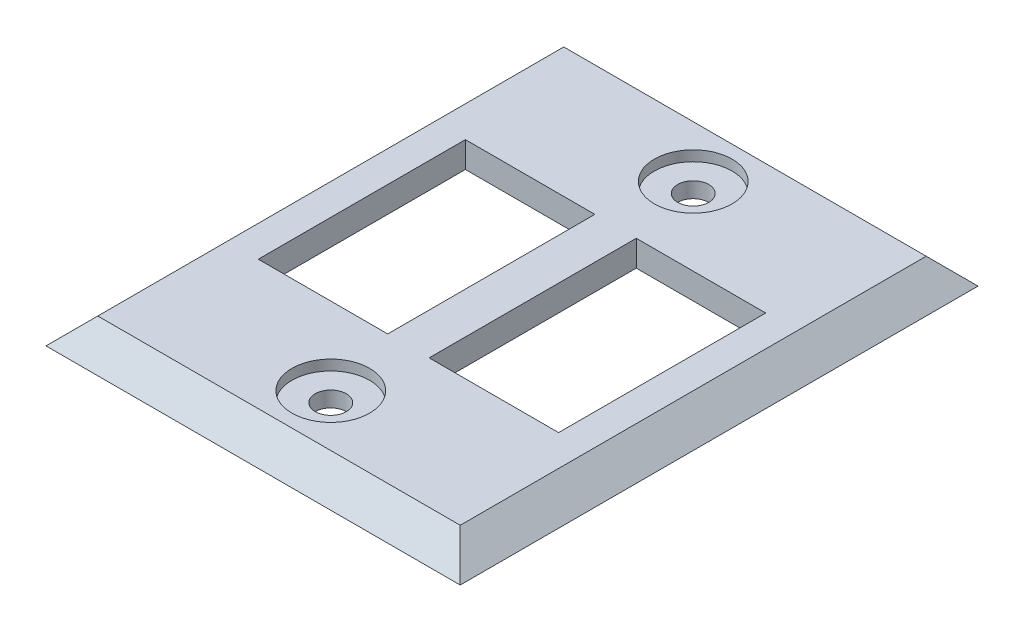
SolidWorks part; units mm, degrees
ref_plane "Front Plane" through (0, 0, 0) normal (0, 0, 1) x (1, 0, 0)
ref_plane "Top Plane" through (0, 0, 0) normal (0, 1, 0) x (1, 0, 0)
ref_plane "Right Plane" through (0, 0, 0) normal (1, 0, 0) x (0, 0, -1)
sketch "Sketch1" plane through (0, 0, 0) normal (0, 1, 0) x (1, 0, 0)
  line L0 (-20, 25) -> (20, -25) construction
  line L1 (-20, 25) -> (20, 25)
  line L2 (-20, 25) -> (-20, -25)
  line L3 (-20, -25) -> (20, -25)
  line L4 (20, 25) -> (20, -25)
  line L5 (-14.5, 10) -> (-2, 10)
  line L6 (-14.5, 10) -> (-14.5, -10)
  line L7 (-14.5, -10) -> (-2, -10)
  line L8 (-2, 10) -> (-2, -10)
  line L9 (0, 0) -> (0, -7.5382) construction
  line L10 (2, 10) -> (2, -10)
  line L11 (14.5, -10) -> (2, -10)
  line L12 (14.5, 10) -> (14.5, -10)
  line L13 (14.5, 10) -> (2, 10)
  line L14 (-2, 10) -> (0, 0) construction
  line L15 (0, 0) -> (-2, -10) construction
  point P9 (0, 0)
  dimension "D1" = 40
  dimension "D2" = 12.5
  dimension "D3" = 20
  dimension "D4" = 50
  dimension "D5" = 29
  dimension "D6" = 2
extrude "Boss-Extrude1" add sketch "Sketch1" along normal blind 2.5
sketch "Sketch2" plane through (0, 2.5, 0) normal (0, 1, 0) x (1, 0, 0)
  line L0 (0, 0) -> (0, -7.7634) construction
  line L1 (-9.6715, 10) -> (0, 17.5) construction
  line L2 (0, 17.5) -> (9.6715, 10) construction
  line L3 (0, 17.5) -> (-9.6715, 25) construction
  line L4 (0, -17.5) -> (9.6715, -10) construction
  line L7 (-9.6715, -10) -> (0, -17.5) construction
  line L8 (0, 16) -> (-12.7123, 16) construction
  line L9 (14.5, 10) -> (2, 10) construction
  line L10 (-13.9598, -16) -> (13.5617, -16) construction
  line L11 (2, -10) -> (14.5, -10) construction
  line L12 (-14.5, -10) -> (-2, -10) construction
  line L13 (-2, 10) -> (-14.5, 10) construction
  line L14 (20, 25) -> (-20, 25) construction
  line L15 (-9.6715, -10) -> (-9.6715, 25) construction
  circle A0 centre (0, 17.5) radius 1.5
  circle A1 centre (0, -17.5) radius 1.5
  point P8 (0, -12.7371)
  point P17 (0, 0)
  point P18 (0, -16.8845)
  point P19 (0, 0)
  dimension "D1" = 3
  dimension "D2" = 32
extrude "Cut-Extrude1" cut sketch "Sketch2" against normal blind 10
sketch "Sketch3" plane through (0, 2.5, 0) normal (0, 1, 0) x (1, 0, 0)
  circle A0 centre (0, 17.5) radius 3.75
  circle A1 centre (0, -17.5) radius 3.75
  point P6 (0, -14.75)
  dimension "D1" = 7.5
extrude "Cut-Extrude2" cut sketch "Sketch3" against normal blind 1
chamfer "Chamfer1" distance 2.5 angle 45 4 edges at (20, 2.5, 0) (0, 2.5, 25) (0, 2.5, -25) (-20, 2.5, 0)
